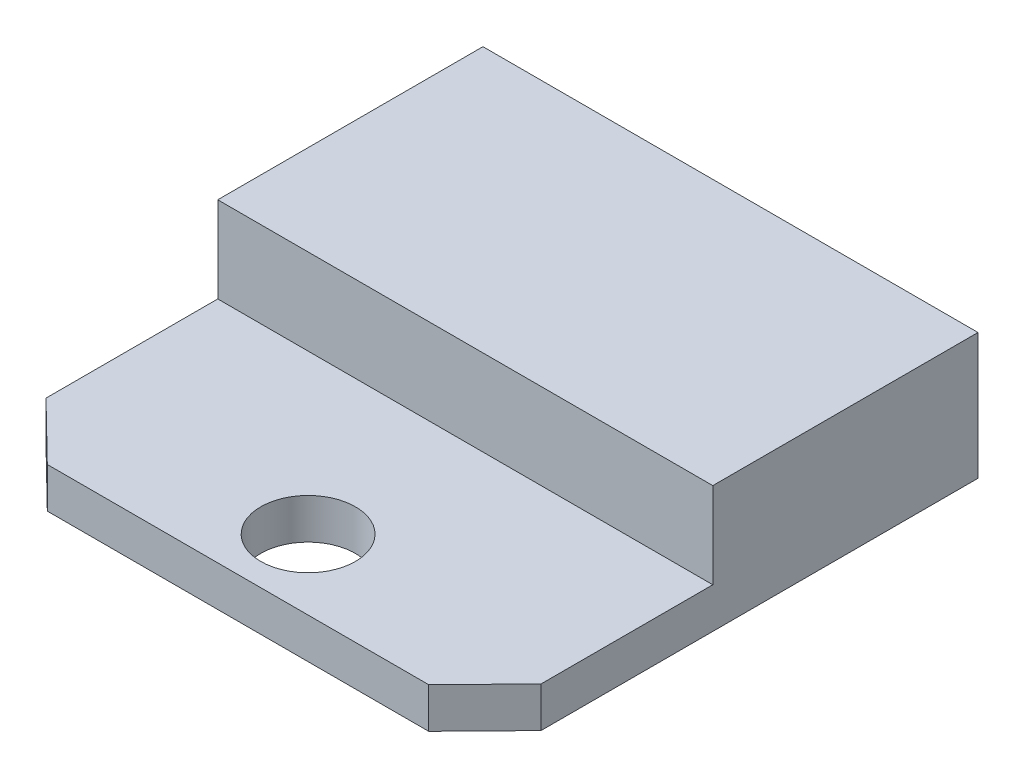
SolidWorks part; units mm, degrees
ref_plane "前视基准面" through (0, 0, 0) normal (0, 0, 1) x (1, 0, 0)
ref_plane "上视基准面" through (0, 0, 0) normal (0, 1, 0) x (1, 0, 0)
ref_plane "右视基准面" through (0, 0, 0) normal (1, 0, 0) x (0, 0, -1)
sketch "草图1" plane through (0, 0, 0) normal (0, 1, 0) x (1, 0, 0)
  line L0 (-9.4058, -12.3149) -> (-9.4058, -5.5149)
  line L1 (-9.4058, -5.5149) -> (10.1942, -5.5149)
  line L2 (10.1942, -5.5149) -> (10.1942, -12.3149)
  line L3 (10.1942, -12.3149) -> (7.996, -14.5649)
  line L4 (7.996, -14.5649) -> (-7.104, -14.5649)
  line L5 (-7.104, -14.5649) -> (-9.4058, -12.3149)
  line L6 (-9.4058, -5.5149) -> (-9.4058, 4.9851)
  line L7 (-9.4058, 4.9851) -> (10.1942, 4.9851)
  line L8 (10.1942, 4.9851) -> (10.1942, -5.5149)
  line L9 (0.446, -14.5649) -> (0.446, 11.1218) construction
  line L10 (-11.4498, -14.5649) -> (12.1098, -14.5649) construction
  circle A0 centre (0.446, -11.7899) radius 1.875
  point P12 (0, 0)
  point P13 (0.446, -11.4562)
  dimension "D2" = 15.1
  dimension "D3" = 6.8
  dimension "D5" = 10.5
extrude "凸台-拉伸1" add sketch "草图1" along normal blind 1.6 contours L5 L4 L3 L2 L1 L0 A0 region at (0.3967, 0, 9.8016)
extrude "凸台-拉伸2" add sketch "草图1<3>" along normal blind 5 contours L8 L7 L6 L1 region at (0.3942, 0, 0.2649)
sketch "草图1<3>" plane through (0, 0, 0) normal (0, 1, 0) x (1, 0, 0) same geometry as "草图1"
